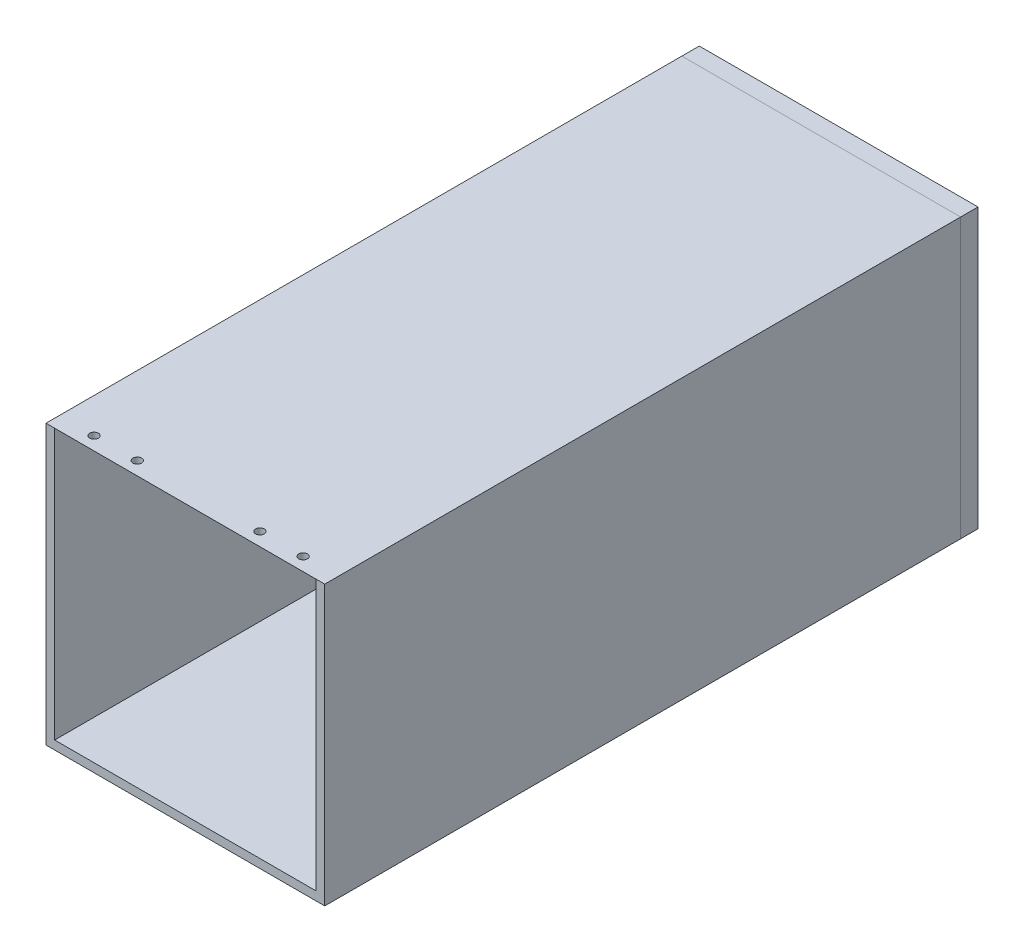
SolidWorks part; units mm, degrees
ref_plane "Front Plane" through (0, 0, 0) normal (0, 0, 1) x (1, 0, 0)
ref_plane "Top Plane" through (0, 0, 0) normal (0, 1, 0) x (1, 0, 0)
ref_plane "Right Plane" through (0, 0, 0) normal (1, 0, 0) x (0, 0, -1)
sketch "Sketch1" plane through (0, 0, 0) normal (0, 0, 1) x (1, 0, 0)
  line L1 (0, 0) -> (-101.6, 0)
  line L2 (0, 0) -> (0, 101.6)
  line L3 (0, 101.6) -> (-101.6, 101.6)
  line L4 (-101.6, 0) -> (-101.6, 101.6)
  line L5 (-98.425, 98.425) -> (-3.175, 98.425)
  line L6 (-98.425, 98.425) -> (-98.425, 3.175)
  line L7 (-98.425, 3.175) -> (-3.175, 3.175)
  line L8 (-3.175, 98.425) -> (-3.175, 3.175)
  dimension "D1" = 101.6
  dimension "D2" = 101.6
  dimension "D3" = 95.25
  dimension "D4" = 95.25
  dimension "D5" = 3.175
  dimension "D6" = 3.175
extrude "Boss-Extrude1" add sketch "Sketch1" along normal blind 231.775
sketch "Sketch2" plane through (0, 0, 0) normal (0, 0, -1) x (-1, 0, 0)
  line L4 (0, 101.6) -> (0, 0)
  line L5 (0, 0) -> (101.6, 0)
  line L6 (101.6, 0) -> (101.6, 101.6)
  line L7 (101.6, 101.6) -> (0, 101.6)
  line L8 (0, 101.6) -> (0, 0)
  line L9 (0, 0) -> (101.6, 0)
  line L10 (101.6, 0) -> (101.6, 101.6)
  line L11 (101.6, 101.6) -> (0, 101.6)
  dimension "D1" = 0
extrude "Boss-Extrude2" add sketch "Sketch2" along normal blind 6.35 separate body
chamfer "Chamfer1" distance 3.175 angle 45 1 edges at (-50.8, 98.425, 231.775)
sketch "Sketch3" plane through (0, 101.6, 0) normal (0, 1, 0) x (1, 0, 0)
  line L0 (-3.175, -231.775) -> (-98.425, -231.775) construction
  line L1 (-101.6, -231.775) -> (-101.6, 0) construction
  line L2 (0, -231.775) -> (0, 0) construction
  circle A0 centre (-88.9, -226.949) radius 1.5875
  circle A1 centre (-73.152, -226.949) radius 1.5875
  circle A2 centre (-28.448, -226.949) radius 1.5875
  circle A3 centre (-12.7, -226.949) radius 1.5875
  point P14 (0, 0)
  dimension "D1" = 3.175
  dimension "D2" = 4.826
  dimension "D3" = 12.7
  dimension "D4" = 12.7
  dimension "D5" = 15.748
  dimension "D6" = 15.748
extrude "Cut-Extrude1" cut sketch "Sketch3" against normal blind 17.78
